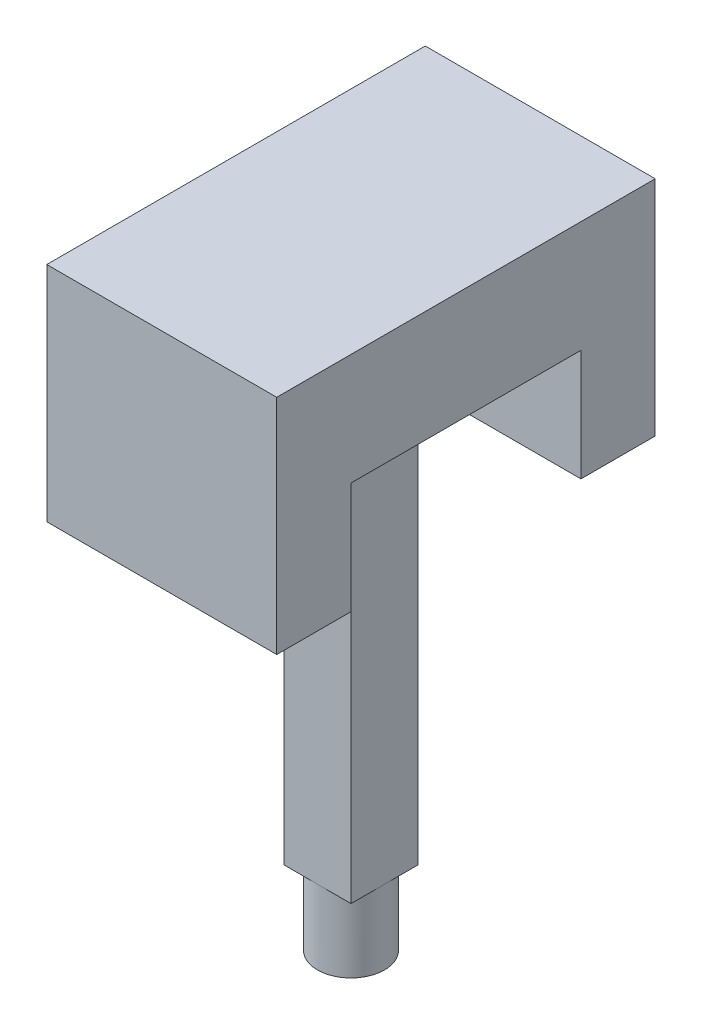
SolidWorks part; units mm, degrees
ref_plane "Front Plane" through (0, 0, 0) normal (0, 0, 1) x (1, 0, 0)
ref_plane "Top Plane" through (0, 0, 0) normal (0, 1, 0) x (1, 0, 0)
ref_plane "Right Plane" through (0, 0, 0) normal (1, 0, 0) x (0, 0, -1)
sketch "Sketch1" plane through (0, 0, 0) normal (0, 1, 0) x (1, 0, 0)
  line L5 (-0.7533, 0.7533) -> (0.7533, 0.7533)
  line L6 (-0.7533, 0.7533) -> (-0.7533, -0.7533)
  line L7 (-0.7533, -0.7533) -> (0.7533, -0.7533)
  line L8 (0.7533, 0.7533) -> (0.7533, -0.7533)
  line L9 (-0.7533, 0.7533) -> (0.7533, -0.7533) construction
  line L10 (-0.7533, -0.7533) -> (0.7533, 0.7533) construction
  point P4 (0, 0)
  dimension "D1" = 1.5067
extrude "Pin" add sketch "Sketch1" along normal blind 10 contours L5 L8 L7 L6
sketch "Sketch2" plane through (0, 0, 0) normal (0, -1, 0) x (1, 0, 0)
  circle A0 centre (0, 0) radius 0.7533
  dimension "D1" = 1.5067
extrude "Tip" add sketch "Sketch2" along normal blind 1.6667
sketch "Sketch3" plane through (0, 10, 0) normal (0, 1, 0) x (1, 0, 0)
  line L1 (-2.58, 2.58) -> (2.58, 2.58)
  line L2 (-2.58, 2.58) -> (-2.58, -2.58)
  line L3 (-2.58, -2.58) -> (2.58, -2.58)
  line L4 (2.58, 2.58) -> (2.58, -2.58)
  line L5 (-2.58, 2.58) -> (2.58, -2.58) construction
  line L6 (-2.58, -2.58) -> (2.58, 2.58) construction
  line L7 (-2.58, 2.58) -> (2.58, 2.58)
  line L8 (-2.58, 2.58) -> (-2.58, 4.2467)
  line L9 (-2.58, 4.2467) -> (2.58, 4.2467)
  line L10 (2.58, 2.58) -> (2.58, 4.2467)
  line L11 (-2.58, 2.58) -> (2.58, 4.2467) construction
  line L12 (-2.58, 4.2467) -> (2.58, 2.58) construction
  line L13 (-2.58, -2.58) -> (2.58, -2.58)
  line L14 (-2.58, -2.58) -> (-2.58, -4.2467)
  line L15 (-2.58, -4.2467) -> (2.58, -4.2467)
  line L16 (2.58, -2.58) -> (2.58, -4.2467)
  line L17 (-2.58, -2.58) -> (2.58, -4.2467) construction
  line L18 (-2.58, -4.2467) -> (2.58, -2.58) construction
  point P4 (0, 0)
  point P10 (0, 3.4133)
  point P13 (0, -3.4133)
  line M5 (-0.7533, 0.7533) -> (-0.7533, -0.7533)
  line M6 (-0.7533, -0.7533) -> (0.7533, -0.7533)
  line M7 (0.7533, -0.7533) -> (0.7533, 0.7533)
  line M8 (0.7533, 0.7533) -> (-0.7533, 0.7533)
  dimension "D1" = 5.16
  dimension "D2" = 1.6667
extrude "Handle" add sketch "Sketch3" along normal blind 2.5 contours L1 L10 L9 L8 | L4 L1 L2 L3 M5 M8 M7 M6 | L16 L3 L14 L15 | M8 M5 M6 M7 region at (0, 10, -3.4133) region at (0, 10, -2.507) region at (0, 10, 3.4133) region at (0, 10, 0)
extrude "Boss-Extrude4" add sketch "Sketch3<3>" against normal blind 2.5 contours L1 L10 L9 L8 | L16 L3 L14 L15 region at (0, 10, -3.4133) region at (0, 10, 3.4133)
sketch "Sketch3<3>" plane through (0, 10, 0) normal (0, 1, 0) x (1, 0, 0) same geometry as "Sketch3"
equation "\"Universal Bar Height\"= 5mm"
equation "\"D1@Sketch1\"=\"Universal Bar Height\"/3 - \"Pin Tolerance\""
equation "\"D1@Sketch2\"=\"Universal Bar Height\"/3 - \"Pin Tolerance\""
equation "\"D1@Tip\" = \"Universal Bar Height\" / 3"
equation "\"D1@Sketch3\"=\"Universal Bar Height\" + \"Pin Tolerance\""
equation "\"D2@Sketch3\"=\"Universal Bar Height\"/3"
equation "\"D1@Handle\" = \"Universal Bar Height\" / 2"
equation "\"Pin Tolerance\"= 0.16mm'The total subtracted width of the pin so it won't grip the sliders too much"
